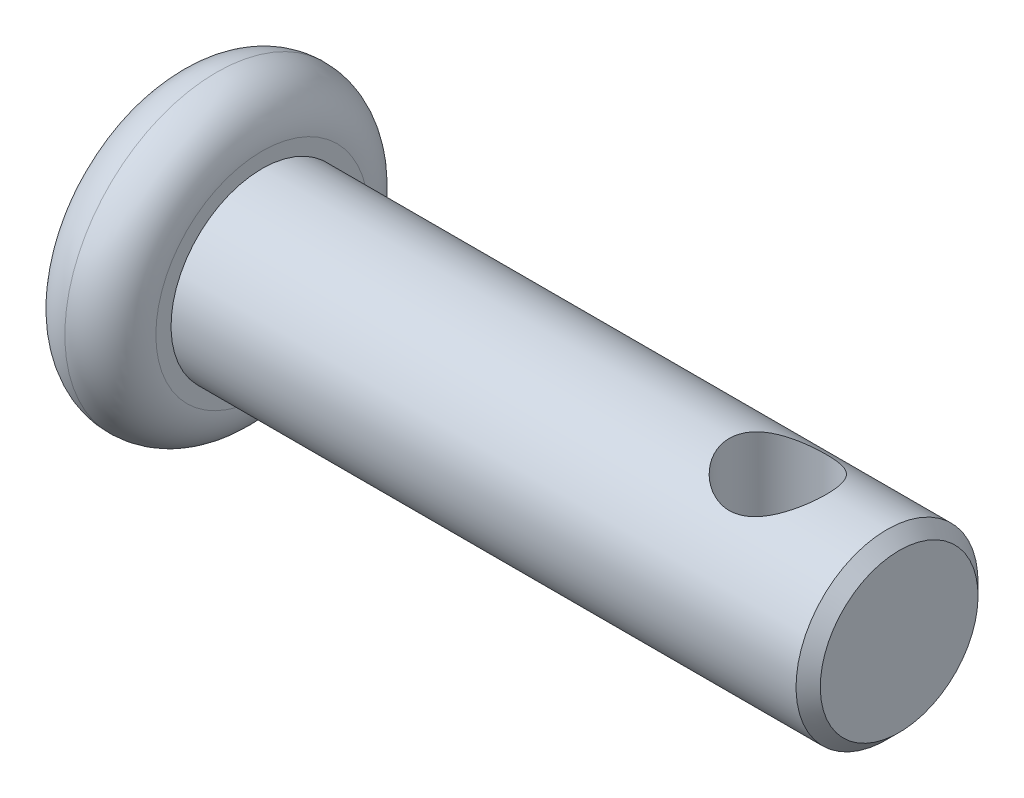
SolidWorks part; units mm, degrees
ref_plane "前视基准面" through (0, 0, 0) normal (0, 0, 1) x (1, 0, 0)
ref_plane "上视基准面" through (0, 0, 0) normal (0, 1, 0) x (1, 0, 0)
ref_plane "右视基准面" through (0, 0, 0) normal (1, 0, 0) x (0, 0, -1)
sketch "草图1" plane through (0, 0, 0) normal (0, 0, 1) x (1, 0, 0)
  line L0 (0, 0) -> (0, 2.5)
  line L1 (0, 2.5) -> (1.5, 2.5)
  line L2 (1.5, 2.5) -> (1.5, 1.5)
  line L3 (1.5, 1.5) -> (12, 1.5)
  line L4 (12, 1.5) -> (12, 0)
  line L5 (12, 0) -> (0, 0) construction
  line L6 (0, 0) -> (12, 0)
  dimension "D1" = 5
  dimension "D2" = 3
  dimension "D3" = 1.5
  dimension "D4" = 12
revolve "旋转1" add sketch "草图1" angle 360 about L5
sketch "草图2" plane through (0, 0, 0) normal (0, 1, 0) x (1, 0, 0)
  line L0 (12, -1.5) -> (12, 1.5) construction
  circle A0 centre (10, 0) radius 0.8
  dimension "D1" = 1.6
  dimension "D2" = 2
extrude "切除-拉伸1" cut sketch "草图2" against normal mid plane 20
chamfer "倒角1" distance 0.2 angle 45 1 edges at (12, 1.5, 0)
fillet "圆角1" radius 0.75 2 edges at (0, 2.5, 0) (1.5, 2.5, 0)
